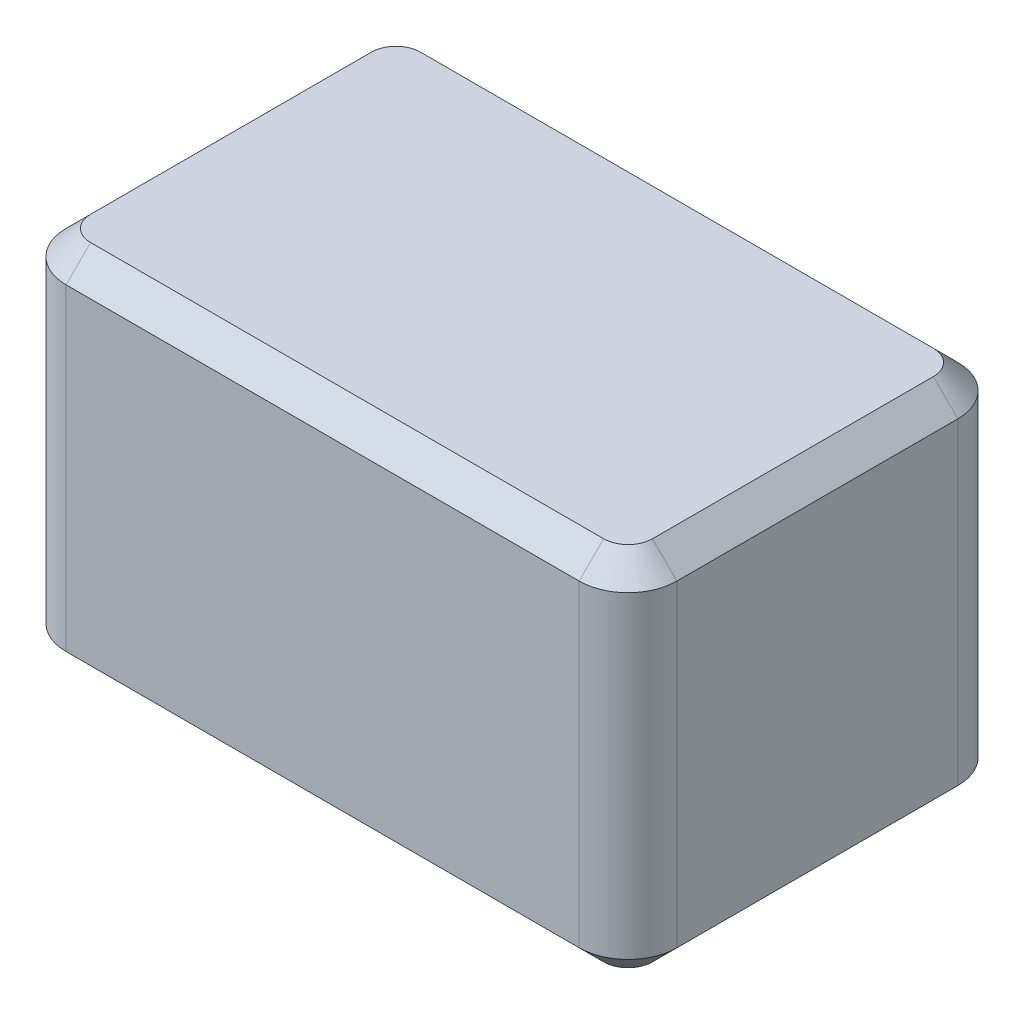
SolidWorks part; units mm, degrees
material "6061 Alloy"
ref_plane "Front Plane" through (0, 0, 0) normal (0, 0, 1) x (1, 0, 0)
ref_plane "Top Plane" through (0, 0, 0) normal (0, 1, 0) x (1, 0, 0)
ref_plane "Right Plane" through (0, 0, 0) normal (1, 0, 0) x (0, 0, -1)
sketch "Sketch1" plane through (0, 0, 0) normal (0, 1, 0) x (1, 0, 0)
  line L1 (0, 0.8401) -> (25, 0.8401)
  line L2 (0, 0.8401) -> (0, 16.3401)
  line L3 (0, 16.3401) -> (25, 16.3401)
  line L4 (25, 0.8401) -> (25, 16.3401)
  line L7 (-10.6625, 16.3401) -> (35.6625, 16.3401) construction
  line L8 (35.6625, 0.8401) -> (-10.6625, 0.8401) construction
  point P5 (0, 0)
  point P6 (25, 14.7064)
  point P9 (25, 14.7064)
  point P10 (0, 0)
  point P13 (0, 0)
  dimension "D1" = 25
extrude "Boss-Extrude1" add sketch "Sketch1" along normal blind 15
fillet "Fillet1" radius 2 4 edges at (25, 7.5, -0.8401) (25, 7.5, -16.3401) (0, 7.5, -16.3401) (0, 7.5, -0.8401)
chamfer "Chamfer1" distance 1 angle 45 16 edges at (12.5, 15, -16.3401) (0.5858, 15, -15.7543) (24.4142, 15, -15.7543) (0, 15, -8.5901) (25, 15, -8.5901) (0.5858, 15, -1.4259) (24.4142, 15, -1.4259) (12.5, 15, -0.8401) (12.5, 0, -16.3401) (0.5858, 0, -15.7543) (24.4142, 0, -15.7543) (0, 0, -8.5901) (25, 0, -8.5901) (0.5858, 0, -1.4259) (24.4142, 0, -1.4259) (12.5, 0, -0.8401)
